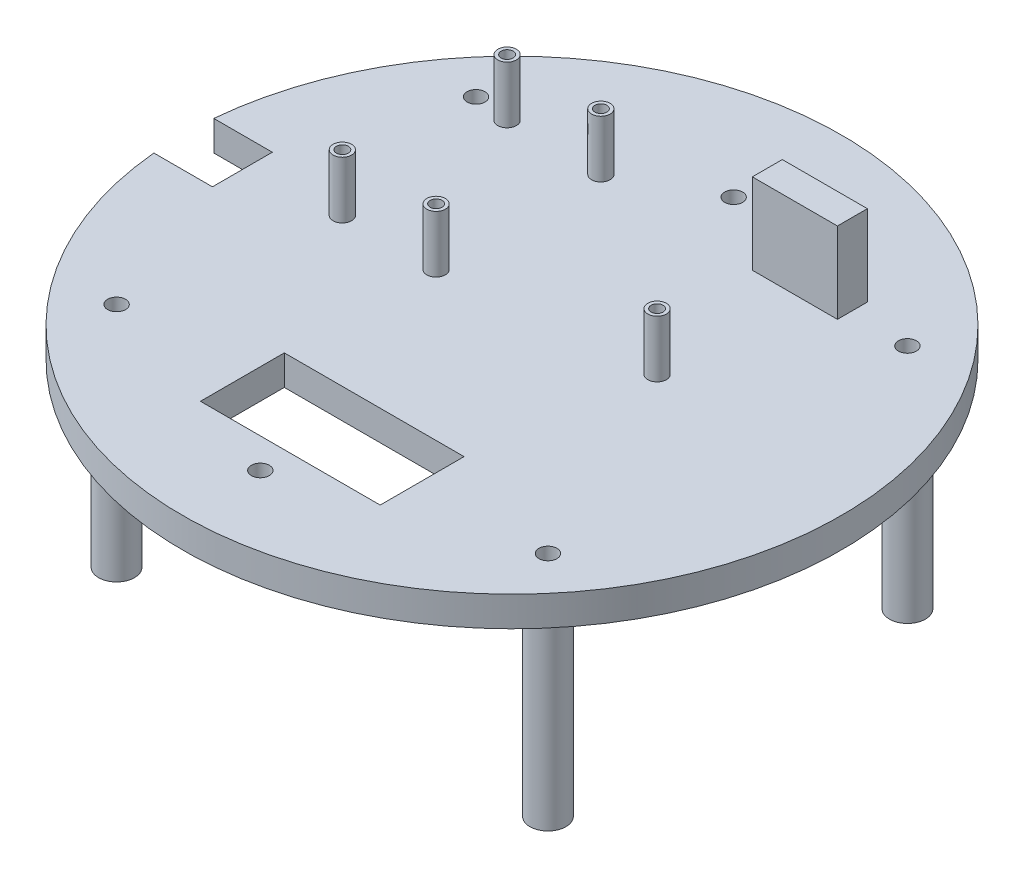
SolidWorks part; units mm, degrees
ref_plane "Front Plane" through (0, 0, 0) normal (0, 0, 1) x (1, 0, 0)
ref_plane "Top Plane" through (0, 0, 0) normal (0, 1, 0) x (1, 0, 0)
ref_plane "Right Plane" through (0, 0, 0) normal (1, 0, 0) x (0, 0, -1)
sketch "Sketch2" plane through (0, 0, 0) normal (0, 1, 0) x (1, 0, 0)
  line L0 (0, 0) -> (9.1621, 0) construction
  line L1 (0, 0) -> (0, 13.2968) construction
  line L3 (-15, -23) -> (15, -23)
  line L4 (-15, -23) -> (-15, -37)
  line L5 (-15, -37) -> (15, -37)
  line L6 (15, -23) -> (15, -37)
  line L7 (-15, -23) -> (15, -37) construction
  line L8 (-15, -37) -> (15, -23) construction
  circle A0 centre (0, 0) radius 55
  point P5 (0, -30)
  point P15 (-40, 0)
  dimension "D1" = 110
  dimension "D2" = 14
  dimension "D3" = 30
  dimension "D4" = 30
extrude "Boss-Extrude1" add sketch "Sketch2" along normal blind 5
sketch "Sketch3" plane through (0, 0, 0) normal (0, -1, 0) x (1, 0, 0)
  line L0 (-15, 0) -> (-15, 12.9052) construction
  line L5 (0, 0) -> (14.6599, 0) construction
  circle A0 centre (-36.95, 10.6) radius 2.5
  circle A4 centre (-36.95, -10.6) radius 2.5
  circle A5 centre (6.95, -10.6) radius 2.5
  circle A6 centre (6.95, 10.6) radius 2.5
  point P0 (0, 0)
  dimension "D3" = 5
  dimension "D1" = 10.6
  dimension "D2" = 21.95
  dimension "D10" = 15
extrude "Boss-Extrude2" add sketch "Sketch3" along normal blind 6
sketch "Sketch15" plane through (0, 5, 0) normal (0, 1, 0) x (1, 0, 0)
  line L0 (-22.2011, 29.3371) -> (-22.2011, 35.4897) construction
  line L7 (-21.0891, 15.4599) -> (-18.0632, 15.4599) construction
  circle A0 centre (-30.0261, 29.2099) radius 1.55
  circle A1 centre (-14.3761, 29.2099) radius 1.55
  circle A2 centre (-14.3761, 1.7099) radius 1.55
  circle A3 centre (-30.0261, 1.7099) radius 1.55
  dimension "D3" = 3.1
  dimension "D6" = 7.825
  dimension "D5" = 15.4599
  dimension "D7" = 13.75
  dimension "D1" = 13.75
  dimension "D2" = 22.2011
  dimension "D4" = 7.825
hole_wizard "Ø2.5mm Dowel Hole2" positions "3DSketch12" profile "Sketch22" hole size "Ø2.5" standard "DIN"
sketch3d "3DSketch12"
  line L0 (-36.95, -6, 10.6) -> (-36.95, 0, 10.6) construction
  line L1 (6.95, -6, 10.6) -> (6.95, 0, 10.6) construction
  line L2 (6.95, -6, -10.6) -> (6.95, 0, -10.6) construction
  line L3 (-36.95, -6, -10.6) -> (-36.95, 0, -10.6) construction
  point P0 (-36.95, -6, 10.6)
  point P4 (6.95, -6, 10.6)
  point P8 (6.95, -6, -10.6)
  point P12 (-36.95, -6, -10.6)
sketch "Sketch22" plane through (-36.95, -6, 10.6) normal (1, 0, 0) x (0, 0, -1)
  line L0 (0, 0) -> (0, 10.9011)
  line L1 (0, 10.9011) -> (1.25, 10.15)
  line L2 (1.25, 10.15) -> (1.25, 0)
  line L5 (1.25, 0) -> (0, 0)
  line L10 (0, 10.9011) -> (-1.25, 10.15) construction
  line L11 (0, -6.35) -> (0, 107.95) construction
  dimension "Hole Dia." = 2.5
  dimension "Hole Depth" = 10.15
  dimension "Drill Angle" = 118
extrude "Boss-Extrude3" add sketch "Sketch15" along normal blind 9.5
hole_wizard "Ø2.0mm Dowel Hole1" positions "3DSketch10" profile "Sketch16" hole size "Ø2.0" standard "DIN"
sketch3d "3DSketch10"
  line L0 (-30.0261, 14.5, -29.2099) -> (-30.0261, 5, -29.2099) construction
  line L1 (-30.0261, 14.5, -1.7099) -> (-30.0261, 5, -1.7099) construction
  line L2 (-14.3761, 14.5, -1.7099) -> (-14.3761, 5, -1.7099) construction
  line L3 (-14.3761, 14.5, -29.2099) -> (-14.3761, 5, -29.2099) construction
  point P0 (-30.0261, 14.5, -29.2099)
  point P4 (-30.0261, 14.5, -1.7099)
  point P8 (-14.3761, 14.5, -1.7099)
  point P12 (-14.3761, 14.5, -29.2099)
sketch "Sketch16" plane through (-30.0261, 14.5, -29.2099) normal (1, 0, 0) x (0, 0, 1)
  line L0 (0, 0) -> (0, 10.7509)
  line L1 (0, 10.7509) -> (1, 10.15)
  line L2 (1, 10.15) -> (1, 0)
  line L5 (1, 0) -> (0, 0)
  line L10 (0, 10.7509) -> (-1, 10.15) construction
  line L11 (0, -6.35) -> (0, 107.95) construction
  dimension "Hole Dia." = 2
  dimension "Hole Depth" = 10.15
  dimension "Drill Angle" = 118
sketch "Sketch17" plane through (0, 5, 0) normal (0, 1, 0) x (1, 0, 0)
  line L1 (12.1174, 33) -> (26.3174, 33)
  line L2 (12.1174, 33) -> (12.1174, 28)
  line L3 (12.1174, 28) -> (26.3174, 28)
  line L4 (26.3174, 33) -> (26.3174, 28)
  line L5 (12.1174, 33) -> (26.3174, 28) construction
  line L6 (12.1174, 28) -> (26.3174, 33) construction
  circle A0 centre (19.2174, 5) radius 1.55
  point P2 (19.2174, 30.5)
  dimension "D1" = 3.1
  dimension "D2" = 5
  dimension "D3" = 19.2174
  dimension "D4" = 23
  dimension "D5" = 14.2
  dimension "D6" = 5
extrude "Boss-Extrude4" add sketch "Sketch17" along normal blind 9.5
hole_wizard "Ø2.0mm Dowel Hole2" positions "3DSketch11" profile "Sketch18" hole size "Ø2.0" standard "DIN"
sketch3d "3DSketch11"
  line L0 (19.2174, 14.5, -5) -> (19.2174, 5, -5) construction
  point P0 (19.2174, 14.5, -5)
sketch "Sketch18" plane through (19.2174, 14.5, -5) normal (1, 0, 0) x (0, 0, 1)
  line L0 (0, 0) -> (0, 10.7509)
  line L1 (0, 10.7509) -> (1, 10.15)
  line L2 (1, 10.15) -> (1, 0)
  line L5 (1, 0) -> (0, 0)
  line L10 (0, 10.7509) -> (-1, 10.15) construction
  line L11 (0, -6.35) -> (0, 107.95) construction
  dimension "Hole Dia." = 2
  dimension "Hole Depth" = 10.15
  dimension "Drill Angle" = 118
sketch "Sketch19" plane through (0, 14.5, 0) normal (0, 1, 0) x (1, 0, 0)
  line L0 (26.3174, 28) -> (26.3174, 33) construction
  line L1 (12.1174, 28) -> (26.3174, 28) construction
  line L2 (12.1174, 33) -> (12.1174, 28) construction
  line L3 (26.3174, 33) -> (12.1174, 33) construction
  line L4 (26.3174, 28) -> (26.3174, 33)
  line L5 (12.1174, 28) -> (26.3174, 28)
  line L6 (12.1174, 33) -> (12.1174, 28)
  line L7 (26.3174, 33) -> (12.1174, 33)
extrude "Boss-Extrude5" add sketch "Sketch19" along normal blind 4
sketch "Sketch21" plane through (0, 5, 0) normal (0, 1, 0) x (1, 0, 0)
  line L8 (0, 0) -> (25.1353, 0) construction
  line L13 (25.1353, 0) -> (0, 0) construction
  line L14 (0, 0) -> (0, 20.9244) construction
  line L15 (-45, 5) -> (-45, -5)
  line L16 (-45, 5) -> (-55, 5)
  line L17 (-45, -5) -> (-55, -5)
  line L18 (-55, 5) -> (-55, -5)
  circle A2 centre (0, 0) radius 55 construction
  point P10 (-45, 0)
  dimension "D1" = 10
  dimension "D2" = 10
  dimension "D3" = 0
extrude "Cut-Extrude1" cut sketch "Sketch21" against normal through all
sketch "Sketch26" plane through (0, 0, 0) normal (0, -1, 0) x (1, 0, 0)
  line L0 (0, 0) -> (44.0399, 0) construction
  line L1 (0, 0) -> (0, 31.9864) construction
  circle A0 centre (0, 42) radius 3
  circle A1 centre (0, -37) radius 3
  dimension "D1" = 6
  dimension "D2" = 6
  dimension "D3" = 42
  dimension "D4" = 37
extrude "Boss-Extrude7" add sketch "Sketch26" along normal blind 3
hole_wizard "Ø3.0mm Dowel Hole2" positions "3DSketch14" profile "Sketch27" hole size "Ø3.0" standard "DIN" end condition through all
sketch3d "3DSketch14"
  line L0 (0, -3, 42) -> (0, 0, 42) construction
  line L1 (0, -3, -37) -> (0, 0, -37) construction
  point P0 (0, -3, 42)
  point P4 (0, -3, -37)
sketch "Sketch27" plane through (0, -3, 42) normal (1, 0, 0) x (0, 0, -1)
  line L0 (0, 0) -> (0, 21.5)
  line L1 (0, 21.5) -> (1.5, 21.5)
  line L2 (1.5, 21.5) -> (1.5, 0)
  line L5 (1.5, 0) -> (0, 0)
  line L11 (0, -6.35) -> (0, 107.95) construction
  dimension "Thru Hole Dia." = 3
  dimension "Thru Hole Depth" = 21.5
sketch "Sketch30" plane through (0, 0, 0) normal (0, -1, 0) x (1, 0, 0)
  line L0 (0, 0) -> (0, 26.3182) construction
  line L1 (0, 0) -> (19.571, 0) construction
  circle A0 centre (-36, 30) radius 3
  circle A1 centre (36, 30) radius 3
  circle A2 centre (36, -30) radius 3
  circle A3 centre (-36, -30) radius 3
  dimension "D1" = 6
  dimension "D2" = 36
  dimension "D3" = 30
extrude "Boss-Extrude9" add sketch "Sketch30" along normal blind 33
hole_wizard "Ø3.0mm Dowel Hole4" positions "3DSketch16" profile "Sketch31" hole size "Ø3.0" standard "DIN" end condition through all
sketch3d "3DSketch16"
  line L0 (-36, -33, 30) -> (-36, 0, 30) construction
  line L1 (36, -33, 30) -> (36, 0, 30) construction
  line L2 (36, -33, -30) -> (36, 0, -30) construction
  line L3 (-36, -33, -30) -> (-36, 0, -30) construction
  point P0 (-36, -33, 30)
  point P4 (36, -33, 30)
  point P8 (36, -33, -30)
  point P12 (-36, -33, -30)
sketch "Sketch31" plane through (-36, -33, 30) normal (1, 0, 0) x (0, 0, -1)
  line L0 (0, 0) -> (0, 51.5)
  line L1 (0, 51.5) -> (1.5, 51.5)
  line L2 (1.5, 51.5) -> (1.5, 0)
  line L5 (1.5, 0) -> (0, 0)
  line L11 (0, -6.35) -> (0, 107.95) construction
  dimension "Thru Hole Dia." = 3
  dimension "Thru Hole Depth" = 51.5
equation "\"D2@Sketch26\"=\"D1@Sketch26\""
